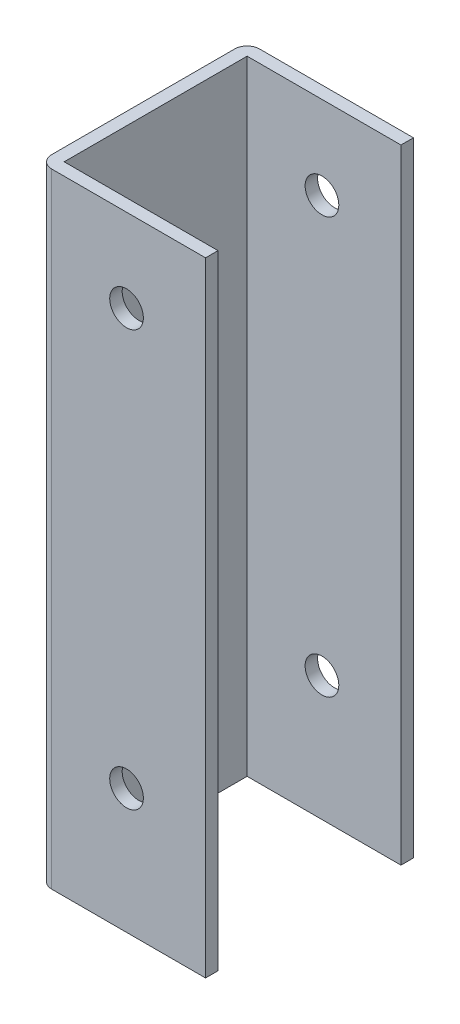
SolidWorks part; units mm, degrees
ref_plane "Спереди" through (0, 0, 0) normal (0, 0, 1) x (1, 0, 0)
ref_plane "Сверху" through (0, 0, 0) normal (0, 1, 0) x (1, 0, 0)
ref_plane "Справа" through (0, 0, 0) normal (1, 0, 0) x (0, 0, -1)
sketch "Эскиз1" plane through (0, 0, 0) normal (0, 1, 0) x (1, 0, 0)
  line L1 (-37, 25) -> (37, 25)
  line L2 (-40, 22) -> (-40, -22)
  line L3 (-37, -25) -> (37, -25)
  line L4 (40, 22) -> (40, -22)
  line L5 (-40, 25) -> (40, -25) construction
  line L6 (-40, -25) -> (40, 25) construction
  arc A0 (-37, 25) -> (-40, 22) centre (-37, 22) ccw
  arc A1 (-40, -22) -> (-37, -25) centre (-37, -22) ccw
  arc A2 (37, -25) -> (40, -22) centre (37, -22) ccw
  arc A3 (37, 25) -> (40, 22) centre (37, 22) cw
  point P0 (0, 0)
  dimension "D1" = 3
extrude "Вытянуть-Тонкостенный1" add sketch "Эскиз1" along normal blind 150 thin thin type one direction reverse wall 3
sketch "Эскиз2" plane through (0, 150, 0) normal (0, 1, 0) x (1, 0, 0)
  line L1 (0, -27.4206) -> (41.1465, -27.4206)
  line L2 (0, -27.4206) -> (0, 30.9728)
  line L3 (0, 30.9728) -> (41.1465, 30.9728)
  line L4 (41.1465, -27.4206) -> (41.1465, 30.9728)
extrude "Вырез-Вытянуть1" cut sketch "Эскиз2" against normal through all
sketch "Эскиз3" plane through (0, 0, -25) normal (0, 0, -1) x (-1, 0, 0)
  circle A0 centre (19, 130) radius 4.05
  circle A1 centre (19, 30) radius 4.05
  dimension "D1" = 2
extrude "Вырез-Вытянуть2" cut sketch "Эскиз3" against normal through all
